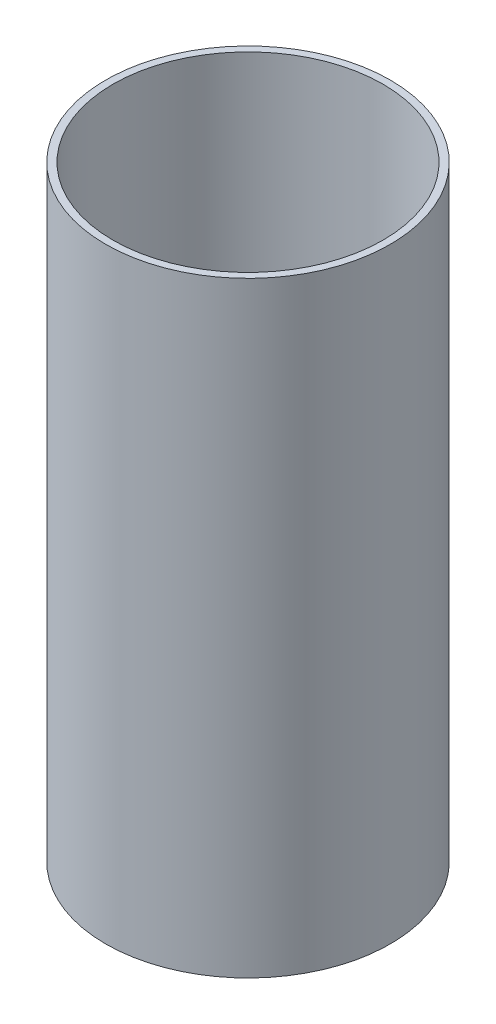
SolidWorks part; units mm, degrees
material "PVC Rigid"
ref_plane "Front Plane" through (0, 0, 0) normal (0, 0, 1) x (1, 0, 0)
ref_plane "Top Plane" through (0, 0, 0) normal (0, 1, 0) x (1, 0, 0)
ref_plane "Right Plane" through (0, 0, 0) normal (1, 0, 0) x (0, 0, -1)
sketch "Sketch1" plane through (0, 0, 0) normal (0, 1, 0) x (1, 0, 0)
  circle A0 centre (0, 0) radius 93.6625
  circle A1 centre (0, 0) radius 88.9
  dimension "D1" = 187.325
  dimension "D2" = 177.8
extrude "Boss-Extrude1" add sketch "Sketch1" along normal mid plane 398.78
